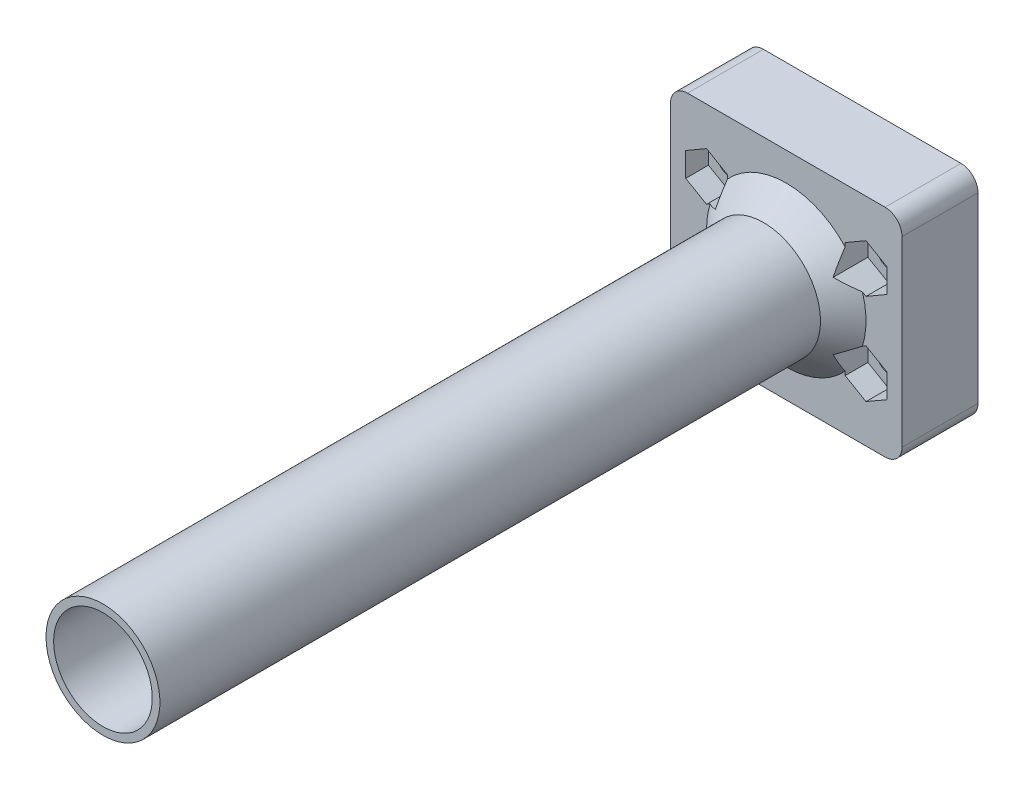
SolidWorks part; units mm, degrees
ref_plane "Front Plane" through (0, 0, 0) normal (0, 0, 1) x (1, 0, 0)
ref_plane "Top Plane" through (0, 0, 0) normal (0, 1, 0) x (1, 0, 0)
ref_plane "Right Plane" through (0, 0, 0) normal (1, 0, 0) x (0, 0, -1)
sketch "Sketch1" plane through (0, 0, 0) normal (0, 0, 1) x (1, 0, 0)
  line L9 (-13.0097, 28.5) -> (13.0097, 28.5)
  line L17 (15.25, 26.2597) -> (15.25, 2.2403)
  line L18 (13.0097, 0) -> (-13.0097, 0)
  line L19 (-15.25, 2.2403) -> (-15.25, 26.2597)
  arc A12 (-15.25, 2.2403) -> (-13.0097, 0) centre (-13.0097, 2.2403) ccw
  arc A13 (13.0097, 0) -> (15.25, 2.2403) centre (13.0097, 2.2403) ccw
  arc A14 (15.25, 26.2597) -> (13.0097, 28.5) centre (13.0097, 26.2597) ccw
  arc A15 (-13.0097, 28.5) -> (-15.25, 26.2597) centre (-13.0097, 26.2597) ccw
  circle A16 centre (-10.5, 20.25) radius 1.5
  circle A17 centre (10.5, 20.25) radius 1.5
  circle A18 centre (10.5, 8.25) radius 1.5
  circle A19 centre (-10.5, 8.25) radius 1.5
  point P11 (-15.25, 0)
  point P14 (15.25, 0)
  point P17 (15.25, 28.5)
  point P21 (-15.25, 28.5)
  dimension "D1" = 2.2403
  dimension "D2" = 2.2403
  dimension "D3" = 2.2403
  dimension "D4" = 2.2403
extrude "Boss-Extrude1" add sketch "Sketch1" along normal blind 10
sketch "Sketch2" plane through (0, 0, 10) normal (0, 0, 1) x (1, 0, 0)
  line L13 (-10.5, 23.4254) -> (-13.25, 21.8377)
  line L14 (-13.25, 21.8377) -> (-13.25, 18.6623)
  line L15 (-13.25, 18.6623) -> (-10.5, 17.0746)
  line L16 (-10.5, 17.0746) -> (-7.75, 18.6623)
  line L17 (-7.75, 18.6623) -> (-7.75, 21.8377)
  line L18 (-7.75, 21.8377) -> (-10.5, 23.4254)
  line L19 (-10.5, 11.4254) -> (-13.25, 9.8377)
  line L20 (-13.25, 9.8377) -> (-13.25, 6.6623)
  line L21 (-13.25, 6.6623) -> (-10.5, 5.0746)
  line L22 (-10.5, 5.0746) -> (-7.75, 6.6623)
  line L23 (-7.75, 6.6623) -> (-7.75, 9.8377)
  line L24 (-7.75, 9.8377) -> (-10.5, 11.4254)
  line L25 (10.5, 23.4254) -> (7.75, 21.8377)
  line L26 (7.75, 21.8377) -> (7.75, 18.6623)
  line L27 (7.75, 18.6623) -> (10.5, 17.0746)
  line L28 (10.5, 17.0746) -> (13.25, 18.6623)
  line L29 (13.25, 18.6623) -> (13.25, 21.8377)
  line L30 (13.25, 21.8377) -> (10.5, 23.4254)
  line L31 (10.5, 11.4254) -> (7.75, 9.8377)
  line L32 (7.75, 9.8377) -> (7.75, 6.6623)
  line L33 (7.75, 6.6623) -> (10.5, 5.0746)
  line L34 (10.5, 5.0746) -> (13.25, 6.6623)
  line L35 (13.25, 6.6623) -> (13.25, 9.8377)
  line L36 (13.25, 9.8377) -> (10.5, 11.4254)
  circle A0 centre (-10.5, 20.25) radius 1.5
  circle A1 centre (-10.5, 20.25) radius 2.75 construction
  circle A2 centre (-10.5, 8.25) radius 2.75 construction
  circle A3 centre (10.5, 20.25) radius 2.75 construction
  circle A4 centre (10.5, 8.25) radius 2.75 construction
  dimension "D1" = 5.5
  dimension "D2" = 6.3509
  dimension "D3" = 5.5
  dimension "D4" = 5.5
  dimension "D5" = 5.5
extrude "Cut-Extrude2" cut sketch "Sketch2" against normal blind 3 contours L13 L14 L15 L16 L17 L18 | L25 L26 L27 L28 L29 L30 | L19 L20 L21 L22 L23 L24 | L31 L32 L33 L34 L35 L36
sketch "Sketch3" plane through (0, 0, 10) normal (0, 0, 1) x (1, 0, 0)
  circle A0 centre (0, 14.25) radius 7.5
  circle A3 centre (0, 14.25) radius 6.5
  point P6 (0, 14.25)
  dimension "D2" = 1
  dimension "D1" = 15
extrude "Boss-Extrude2" add sketch "Sketch3" along normal blind 90
chamfer "Chamfer1" distance 3 angle 45 1 edges at (7.5, 14.25, 10)
